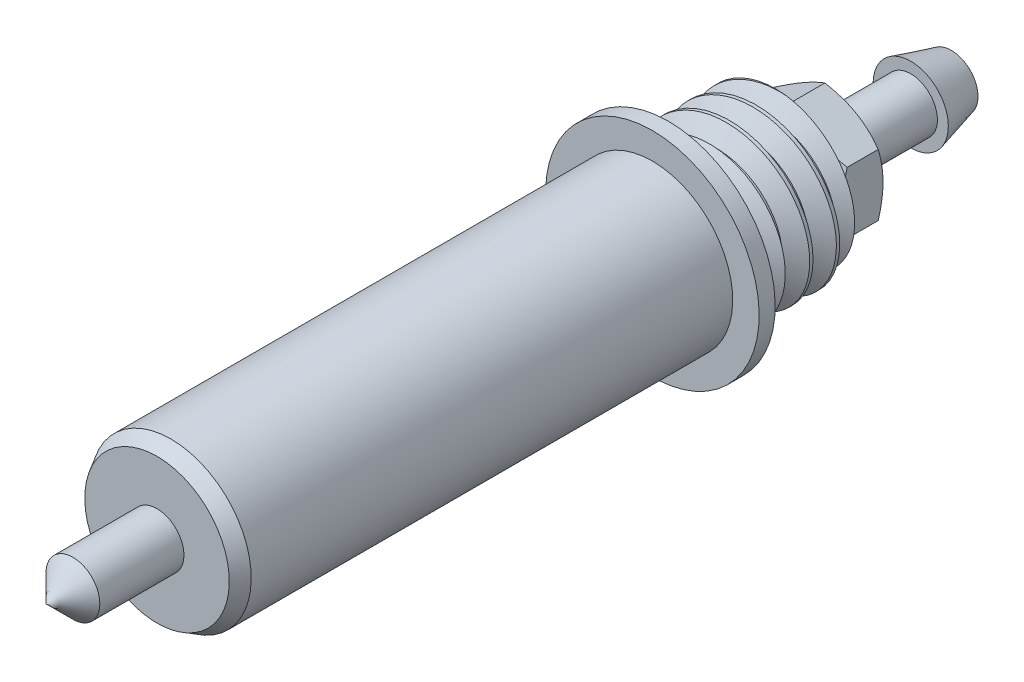
SolidWorks part; units mm, degrees
ref_plane "Front Plane" through (0, 0, 0) normal (0, 0, 1) x (1, 0, 0)
ref_plane "Top Plane" through (0, 0, 0) normal (0, 1, 0) x (1, 0, 0)
ref_plane "Right Plane" through (0, 0, 0) normal (1, 0, 0) x (0, 0, -1)
sketch "Sketch1" plane through (0, 0, 0) normal (1, 0, 0) x (0, 0, -1)
  line L0 (16.637, 0) -> (-16.637, 0) construction
  line L1 (0, -2.3876) -> (0, 2.3876) construction
  line L2 (-16.637, 0) -> (-15.8369, 0.8001) construction
  line L3 (16.637, 0.7937) -> (16.637, -0.7937) construction
  line L4 (-16.637, -0.8001) -> (-16.637, 0.8001)
  line L5 (9.017, -2.413) -> (9.017, 2.413) construction
  line L6 (9.017, 2.413) -> (8.2233, 2.413) construction
  line L7 (11.811, -1.5875) -> (11.811, 1.5875) construction
  line L8 (-6.985, 1.9844) -> (-6.985, -1.9844) construction
  line L9 (7.747, -3.175) -> (7.747, 3.175) construction
  point P0 (-10.287, 0)
  point P3 (-6.985, 0)
  point P4 (0, 0)
  point P8 (0, 0)
  point P11 (11.811, 0)
  point P13 (-16.637, 0)
  point P16 (16.637, 0)
  point P17 (7.747, 0)
  point P18 (9.017, 0)
  point P19 (8.382, 0)
  point P23 (11.811, 0)
  point P28 (11.811, 0)
  point P30 (-6.985, 0)
  point P33 (7.747, 0)
  point P36 (8.382, 0)
  dimension "Extended Length" = 33.274
  dimension "OD" = 4.7752
  dimension "Stroke Length" = 6.35
  dimension "Retracted Length" = 26.924
  dimension "Rod Diameter" = 1.6002
  dimension "Rod Tapered End Angle" = 45
  dimension "For Hose ID" = 1.5875
  dimension "Rod Protrusion When Retracted" = 3.302
  dimension "Cylinder Body Length" = 18.796
  dimension "D to Flange" = 4.064
  dimension "Flange Length" = 0.635
  dimension "Thread Length" = 2.794
  dimension "Thread Dia" = 4.826
  dimension "Pitch" = 0.7937
  dimension "Hex Width" = 3.175
  dimension "Bore Size" = 3.9688
  dimension "Flange Dia" = 6.35
sketch "Sketch2" plane through (0, 0, 0) normal (1, 0, 0) x (0, 0, -1)
  line L0 (-6.985, 0.8001) -> (-6.985, 2.1488)
  line L1 (-6.985, 1.9844) -> (-6.985, -1.9844) construction
  line L2 (-6.985, 2.1488) -> (-6.5715, 2.3876)
  line L3 (-6.5715, 2.3876) -> (7.747, 2.3876)
  line L4 (7.747, -3.175) -> (7.747, 3.175) construction
  line L5 (7.747, 2.3876) -> (7.747, 1.7256)
  line L6 (7.747, 1.7256) -> (9.017, 1.7256)
  line L7 (9.017, -2.413) -> (9.017, 2.413) construction
  line L8 (9.017, 1.7256) -> (9.4139, 2.413)
  line L9 (9.4139, 2.413) -> (11.4141, 2.413)
  line L10 (11.4141, 2.413) -> (11.811, 1.7256)
  line L11 (11.811, -1.5875) -> (11.811, 1.5875) construction
  line L12 (9.017, 1.7256) -> (9.017, 2.413) construction
  line L13 (9.017, 2.413) -> (9.4139, 2.413) construction
  line L14 (11.4141, 2.413) -> (11.811, 2.413) construction
  line L15 (11.811, 1.7256) -> (11.811, 1.3224)
  line L16 (11.811, 1.3224) -> (7.3438, 1.3224)
  line L17 (7.3438, 1.3224) -> (7.3438, 1.9844)
  line L18 (7.3438, 1.9844) -> (-6.5818, 1.9844)
  line L19 (-6.5818, 1.9844) -> (-6.5818, 0.8001)
  line L20 (-6.5818, 0.8001) -> (-6.985, 0.8001)
  line L21 (0.381, 1.9844) -> (0.381, 2.3876) construction
  line L22 (7.3438, 1.6534) -> (7.747, 1.6534) construction
  line L23 (-6.985, 2.1488) -> (-6.985, 2.3876) construction
  line L24 (-6.985, 2.3876) -> (-6.5715, 2.3876) construction
  line L25 (7.747, 1.7256) -> (7.747, 1.3224) construction
  dimension "D1" = 30
  dimension "D2" = 0.3969
  dimension "D3" = 30
  dimension "D4" = 0.2388
revolve "Revolve1" add sketch "Sketch2" angle 360 about L0
sketch "Sketch3" plane through (0, 0, 0) normal (1, 0, 0) x (0, 0, -1)
  line L0 (-10.287, 0) -> (-9.4869, 0.8001)
  line L1 (-9.4869, 0.8001) -> (-6.985, 0.8001)
  line L2 (-16.637, 0) -> (-15.8369, 0.8001) construction
  line L3 (-6.985, 0.8001) -> (-0.635, 0.8001)
  line L4 (-10.287, 0) -> (-16.637, 0) construction
  line L5 (-0.635, 0.8001) -> (-0.635, 1.9844)
  line L6 (7.3438, 1.9844) -> (-6.5818, 1.9844) construction
  line L7 (-0.635, 1.9844) -> (3.1242, 1.9844)
  line L8 (3.1242, 1.9844) -> (3.1242, 0)
  line L9 (16.637, 0) -> (-16.637, 0) construction
  line L10 (3.1242, 0) -> (-10.287, 0)
  dimension "D1" = 3.7592
revolve "Revolve2" add sketch "Sketch3" angle 360 about L10
sketch "Sketch4" plane through (0, 0, 0) normal (1, 0, 0) x (0, 0, -1)
  line L0 (9.017, 1.7256) -> (7.747, 1.7256) construction
  line L1 (7.747, 3.175) -> (8.2233, 3.175)
  line L2 (7.747, 3.175) -> (7.747, 1.7256)
  line L3 (7.747, 1.7256) -> (8.2233, 1.7256)
  line L4 (8.2233, 3.175) -> (8.2233, 1.7256)
revolve "Revolve3" add sketch "Sketch4" angle 360 about L0
sketch "Sketch5" plane through (0, 0, 0) normal (1, 0, 0) x (0, 0, -1)
  line L0 (11.811, 0.3969) -> (11.811, 1.5875)
  line L1 (11.811, -1.5875) -> (11.811, 1.5875) construction
  line L2 (11.811, 1.5875) -> (13.0175, 1.5875)
  line L3 (13.0175, 1.5875) -> (13.0175, 0.7937)
  line L4 (13.0175, 0.7937) -> (15.4305, 0.7937)
  line L5 (15.4305, 0.7937) -> (15.4305, 1.117)
  line L6 (15.4305, 1.117) -> (16.637, 0.7937)
  line L7 (16.637, 0.7937) -> (16.637, -0.7937) construction
  line L8 (16.637, 0.7937) -> (16.637, 0.3969)
  line L9 (16.637, 0.3969) -> (11.811, 0.3969)
  line L10 (16.637, 0.7937) -> (16.637, 0) construction
  line L11 (11.811, 0) -> (13.0175, 0) construction
  line L12 (16.637, 0) -> (-16.637, 0) construction
  line L13 (13.0175, 0) -> (14.224, 0) construction
  line L14 (14.224, 0) -> (15.4305, 0) construction
  line L15 (15.4305, 0) -> (16.637, 0) construction
  point P5 (16.637, 0.3969)
  dimension "D1" = 15
revolve "Revolve4" add sketch "Sketch5" angle 360 about L13
sketch "Sketch6" plane through (0, 0, -13.0175) normal (0, 0, -1) x (-1, 0, 0)
  line L1 (0, 1.8331) -> (-1.5875, 0.9165)
  line L2 (-1.5875, 0.9165) -> (-1.5875, -0.9165)
  line L3 (-1.5875, -0.9165) -> (0, -1.8331)
  line L4 (0, -1.8331) -> (1.5875, -0.9165)
  line L5 (1.5875, -0.9165) -> (1.5875, 0.9165)
  line L6 (1.5875, 0.9165) -> (0, 1.8331)
  circle A0 centre (0, 0) radius 0.7937 construction
  circle A1 centre (0, 0) radius 0.7937
  circle A2 centre (0, 0) radius 1.5875 construction
  circle A3 centre (0, 0) radius 1.5875 construction
extrude "Boss-Extrude1" add sketch "Sketch6" against normal up to surface (1.2065 mm away) up to face at (0, -0.3969, -11.811)
sketch "Sketch7" plane through (0, 0, 0) normal (1, 0, 0) x (0, 0, -1)
  line L0 (11.811, 1.5875) -> (11.9528, 1.8331)
  line L1 (11.811, 1.8331) -> (13.0175, 1.8331) construction
  line L2 (11.9528, 1.8331) -> (11.811, 1.8331)
  line L3 (11.811, 1.8331) -> (11.811, 1.5875)
  line L4 (12.8757, 1.8331) -> (13.0175, 1.8331)
  line L5 (13.0175, 1.8331) -> (13.0175, 1.5875)
  line L6 (13.0175, 1.8331) -> (13.0175, 0.9165) construction
  line L7 (13.0175, 1.5875) -> (12.8757, 1.8331)
  dimension "D1" = 30
revolve "Cut-Revolve1" cut sketch "Sketch7" angle 360 about L0
sketch "Sketch12" plane through (0, 0, 0) normal (0, 0, 1) x (1, 0, 0)
  circle A0 centre (0, 0) radius 1.9844 construction
sketch "Sketch11" plane through (0, 0, 0) normal (1, 0, 0) x (0, 0, -1)
  line L0 (-16.637, 0) -> (-15.8369, 0.8001) construction
  line L1 (-15.8369, 0.8001) -> (-6.985, 0.8001) construction
  line L2 (-16.637, 0) -> (-15.8369, -0.8001) construction
  line L3 (-15.8369, -0.8001) -> (-6.985, -0.8001) construction
  point P4 (11.4141, -2.413)
  point P10 (16.637, -0.7937)
ref_plane "Plane1" through (0, 0, -9.017) normal (0, 0, 1) x (1, 0, 0)
split "Split1" trim tools "Plane1" bodies to split 104 resulting bodies 110 111
sketch "Sketch8" plane through (0, 0, -9.017) normal (0, 0, 1) x (1, 0, 0)
  circle A0 centre (0, 0) radius 2.413 construction
  circle A1 centre (0, 0) radius 2.413
curve "Helix/Spiral1" pitch 0.7937 height 3.5877 radius 2.413 centre (0, 0, -9.017) axis (0, 0, -1) start towards (0, 1, 0)
sketch "Sketch9" plane through (0, 0, 0) normal (1, 0, 0) x (0, 0, -1)
  line L0 (8.2729, 2.4989) -> (8.6697, 1.8115) construction
  line L1 (8.6697, 1.8115) -> (9.0666, 2.4989) construction
  line L2 (9.0666, 2.4989) -> (8.2729, 2.4989) construction
  line L3 (8.3225, 2.413) -> (9.017, 2.413) construction
  line L4 (8.6201, 1.8974) -> (8.7193, 1.8974)
  line L5 (8.6697, 2.413) -> (8.6697, 2.4989) construction
  line L6 (8.6697, 1.8974) -> (8.6697, 1.8115) construction
  line L7 (8.6697, 2.456) -> (8.2977, 2.456) construction
  line L8 (8.2977, 2.456) -> (9.0666, 2.4989)
  line L9 (9.0666, 2.4989) -> (8.7193, 1.8974)
  line L10 (8.2977, 2.456) -> (8.6201, 1.8974)
  line L11 (9.017, 1.7256) -> (9.017, -1.7256) construction
  line L12 (11.4141, 2.413) -> (9.4139, 2.413) construction
  dimension "D1" = 0.7937
  dimension "D2" = 0.0992
sweep "Cut-Sweep1" cut profiles "Sketch9" path "Helix/Spiral1" align with end faces yes
combine bodies "Combine1" operation type add bodies to combine 111 112
equation "\"D2@Sketch2\"=\"Pitch@sketch1\"*.5"
equation "\"D1@Sketch3\"=\"Cylinder Body Length@Sketch1\"*.2"
equation "\"D4@Sketch2\"=\"OD@Sketch1\"*.05"
equation "\"D3@Helix/Spiral1\"=\"Thread Length@Sketch1\"+\"Pitch@Sketch1\""
equation "\"D4@Helix/Spiral1\"=\"Pitch@Sketch1\""
equation "\"D1@Sketch9\"=\"Pitch@Sketch1\""
equation "\"D2@Sketch9\"=\"Pitch@Sketch1\"/8"
